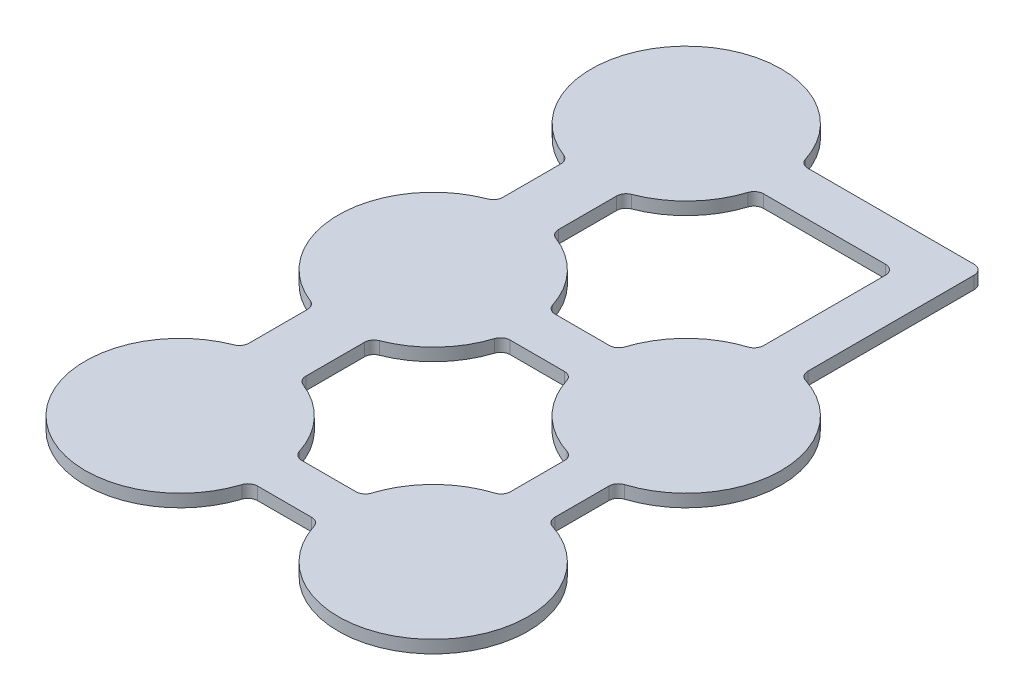
SolidWorks part; units mm, degrees
ref_plane "Front Plane" through (0, 0, 0) normal (0, 0, 1) x (1, 0, 0)
ref_plane "Top Plane" through (0, 0, 0) normal (0, 1, 0) x (1, 0, 0)
ref_plane "Right Plane" through (0, 0, 0) normal (1, 0, 0) x (0, 0, -1)
sketch "Sketch1" plane through (0, 0, 0) normal (0, 1, 0) x (1, 0, 0)
  line L0 (-10, 0) -> (10, 0) construction
  line L1 (-10, 0) -> (-10, 20) construction
  line L2 (-10, 0) -> (-10, -20) construction
  line L3 (-10, -20) -> (10, -20) construction
  line L4 (10, -20) -> (10, 0) construction
  line L6 (-12.2, 12.8299) -> (-7.8, 12.8299)
  line L7 (-12.2, 12.8299) -> (-12.2, 7.1701)
  line L8 (-12.2, 7.1701) -> (-7.8, 7.1701)
  line L9 (-7.8, 12.8299) -> (-7.8, 7.1701)
  line L14 (-12.25, -7.1545) -> (-7.75, -7.1545)
  line L15 (-12.25, -7.1545) -> (-12.25, -12.8455)
  line L16 (-12.25, -12.8455) -> (-7.75, -12.8455)
  line L17 (-7.75, -7.1545) -> (-7.75, -12.8455)
  line L18 (-2.707, -18.25) -> (2.707, -18.25)
  line L19 (-2.707, -18.25) -> (-2.707, -21.75)
  line L20 (-2.707, -21.75) -> (2.707, -21.75)
  line L21 (2.707, -18.25) -> (2.707, -21.75)
  line L22 (8.25, -7.293) -> (11.75, -7.293)
  line L23 (8.25, -7.293) -> (8.25, -12.707)
  line L24 (8.25, -12.707) -> (11.75, -12.707)
  line L25 (11.75, -7.293) -> (11.75, -12.707)
  line L26 (-2.7131, 1.775) -> (2.7131, 1.775)
  line L27 (-2.7131, 1.775) -> (-2.7131, -1.775)
  line L28 (-2.7131, -1.775) -> (2.7131, -1.775)
  line L29 (2.7131, 1.775) -> (2.7131, -1.775)
  line L30 (-2.707, 21.75) -> (11.75, 21.75)
  line L31 (-2.707, 21.75) -> (-2.707, 18.25)
  line L32 (-2.707, 18.25) -> (11.75, 18.25)
  line L33 (11.75, 21.75) -> (11.75, 18.25)
  line L34 (11.75, 7.293) -> (8.25, 7.293)
  line L35 (11.75, 7.293) -> (11.75, 21.75)
  line L36 (11.75, 21.75) -> (8.25, 21.75)
  line L37 (8.25, 7.293) -> (8.25, 21.75)
  circle A0 centre (10, 0) radius 7.5
  circle A1 centre (-10, 0) radius 7.5
  circle A2 centre (-10, 20) radius 7.5
  circle A3 centre (-10, -20) radius 7.5
  circle A4 centre (10, -20) radius 7.5
  point P10 (0, 0)
  point P15 (-10, 12.8299)
  point P33 (-10, -7.1545)
  point P34 (-2.707, -20)
  point P35 (10, -7.293)
  point P36 (-2.7131, 0)
  point P44 (6.0643, 7.5)
  point P45 (0, 0)
  point P46 (0, 0)
  point P47 (0, 0)
  point P48 (0, 0)
  point P49 (0, 0)
  dimension "D1" = 15
  dimension "D2" = 20
  dimension "D3" = 4.4
  dimension "D4" = 4.5
  dimension "D5" = 3.55
  dimension "D6" = 3.5
  dimension "D7" = 3.5
  dimension "D8" = 3.5
extrude "Boss-Extrude1" add sketch "Sketch1" along normal blind 1 contours A3 L17 A1 L15 | A4 L18 A3 L20 | A4 L25 A0 L23 | A0 L35 L32 L37 | A1 L28 A0 L26 | L37 L32 L33 L30 | A2 L32 L37 L30 | A2 L7 A1 L9 | A1 | A3 | A4 | A0 | A2 region at (-10, 0, -10) region at (2.8405, 0, -20) region at (-10, 0, 10) region at (10, 0, -20) region at (0, 0, 0) region at (10, 0, -12.8405) region at (0, 0, 20) region at (10, 0, 10)
fillet "Fillet1" radius 0.75 26 edges at (2.7131, 0.5, -1.775) (-2.7131, 0.5, -1.775) (11.75, 0.5, -21.75) (-2.707, 0.5, -21.75) (8.25, 0.5, -7.293) (11.75, 0.5, -7.293) (11.75, 0.5, 12.707) (2.707, 0.5, 21.75) (-2.707, 0.5, 21.75) (-2.707, 0.5, 18.25) (2.707, 0.5, 18.25) (8.25, 0.5, 12.707) (11.75, 0.5, 7.293) (-2.7131, 0.5, 1.775) (2.7131, 0.5, 1.775) (8.25, 0.5, 7.293) (-12.25, 0.5, 12.8455) (-7.75, 0.5, 12.8455) (-7.75, 0.5, 7.1545) (-12.25, 0.5, 7.1545) (-12.2, 0.5, -7.1701) (-7.8, 0.5, -7.1701) (8.25, 0.5, -18.25) (-2.707, 0.5, -18.25) (-7.8, 0.5, -12.8299) (-12.2, 0.5, -12.8299)
